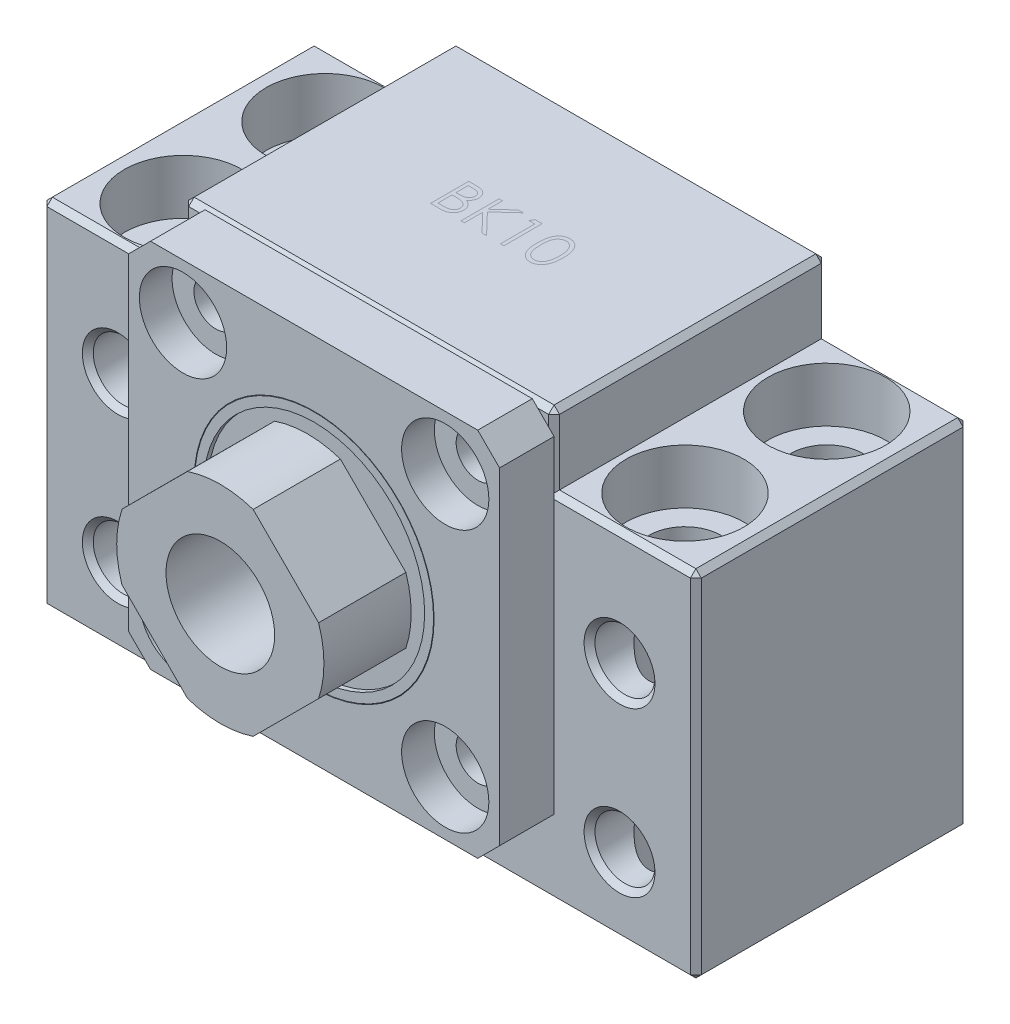
SolidWorks part; units mm, degrees
material "1060 Alloy"
ref_plane "Front Plane" through (0, 0, 0) normal (0, 0, 1) x (1, 0, 0)
ref_plane "Top Plane" through (0, 0, 0) normal (0, 1, 0) x (1, 0, 0)
ref_plane "Right Plane" through (0, 0, 0) normal (1, 0, 0) x (0, 0, -1)
ref_plane "Plane1" through (0, 0, -10) normal (0, 0, -1) x (-1, 0, 0)
sketch "Sketch1" plane through (0, 0, -10) normal (0, 0, -1) x (-1, 0, 0)
  line L0 (30, 0) -> (30, 39) construction
  line L1 (30, 39) -> (-30, 39) construction
  line L2 (-30, 39) -> (-30, 0) construction
  line L3 (-30, 0) -> (30, 0)
  line L4 (30, 32.5) -> (-30, 32.5) construction
  line L5 (0, 39) -> (0, 0) construction
  line L6 (-17, 39) -> (-17, 32.5)
  line L7 (17, 39) -> (17, 32.5)
  line L8 (30, 0) -> (30, 32.5)
  line L9 (-30, 32.5) -> (-30, 0)
  line L10 (-17, 39) -> (17, 39)
  line L11 (30, 32.5) -> (17, 32.5)
  line L12 (-30, 32.5) -> (-17, 32.5)
  line L13 (17, 39) -> (17, 0) construction
  line L14 (-17, 39) -> (-17, 0) construction
  line L16 (23, 7) -> (-23, 7) construction
  line L17 (23, 7) -> (23, 22) construction
  line L18 (23, 22) -> (-23, 22) construction
  line L19 (-23, 7) -> (-23, 22) construction
  line L20 (23, 7) -> (-23, 22) construction
  line L21 (23, 22) -> (-23, 7) construction
  circle A0 centre (-23, 22) radius 2.75
  circle A1 centre (23, 22) radius 2.75
  circle A2 centre (23, 7) radius 2.75
  circle A3 centre (-23, 7) radius 2.75
  point P4 (-30, 19.5)
  point P14 (0, 14.5)
  dimension "D9" = 5.5
  dimension "D10" = 5.5
  dimension "D11" = 5.5
  dimension "D12" = 5.5
  dimension "D1" = 60
  dimension "D2" = 39
  dimension "D3" = 32.5
  dimension "D6" = 15
  dimension "D7" = 22
  dimension "D8" = 46
  dimension "D4" = 17
  dimension "D5" = 17
extrude "Boss-Extrude1" add sketch "Sketch1" against normal blind 25
hole_wizard "Hole1" positions "Sketch5" profile "Sketch4" legacy
sketch "Sketch5" plane through (0, 0, 15) normal (0, 0, -1) x (-1, 0, 0)
  line L0 (30, 0) -> (30, 32.5) construction
  line L1 (-30, 0) -> (30, 0) construction
  point P0 (0, 22)
  dimension "D1" = 30
  dimension "D2" = 22
sketch "Sketch4" plane through (0, 22, 15) normal (1, 0, 0) x (0, -1, 0)
  line L0 (0, 0) -> (0, 25)
  line L1 (0, 25) -> (10.5, 25)
  line L2 (10.5, 25) -> (10.5, 20)
  line L3 (10.5, 20) -> (13, 20)
  line L4 (13, 20) -> (13, 0)
  line L5 (13, 0) -> (0, 0)
  line L6 (0, 110) -> (0, -10) construction
  dimension "Diameter" = 21
  dimension "C-Bore Diameter" = 26
  dimension "C-Bore Depth" = 20
sketch "Sketch10" plane through (0, 32.5, 0) normal (0, 1, 0) x (1, 0, 0)
  line L0 (-30, 4) -> (30, 4) construction
  line L3 (0, 10) -> (0, -15) construction
  line L4 (-17, 10) -> (17, 10) construction
  line L5 (-17, -15) -> (17, -15) construction
  line L7 (17, 10) -> (30, 10) construction
  line L8 (-30, -9) -> (30, -9) construction
  line L9 (-30, -15) -> (-30, 10) construction
  line L10 (30, -15) -> (30, 10) construction
  circle A0 centre (-23, 4) radius 3.3
  circle A1 centre (23, 4) radius 3.3
  circle A2 centre (-23, -9) radius 3.3
  circle A3 centre (23, -9) radius 3.3
  dimension "D1" = 6.6
  dimension "D2" = 6.6
  dimension "D3" = 46
  dimension "D4" = 23
  dimension "D7" = 6.6
  dimension "D8" = 6.6
  dimension "D5" = 6
  dimension "D6" = 13
extrude "Cut-Extrude3" cut sketch "Sketch10" against normal through all
sketch "Sketch11" plane through (0, 32.5, 0) normal (0, 1, 0) x (1, 0, 0)
  circle A0 centre (-23, 4) radius 5.4
  circle A1 centre (23, 4) radius 5.4
  circle A2 centre (-23, -9) radius 5.4
  circle A3 centre (23, -9) radius 5.4
  dimension "D1" = 10.8
  dimension "D2" = 10.8
  dimension "D3" = 10.8
  dimension "D4" = 10.8
extrude "Cut-Extrude4" cut sketch "Sketch11" against normal blind 5
chamfer "Chamfer3" distance 0.5 angle 45 32 edges at (0, 0, -10) (30, 16.25, -10) (23.5, 32.5, -10) (17, 35.75, -10) (0, 39, -10) (-17, 35.75, -10) (-23.5, 32.5, -10) (-30, 16.25, -10) (20.25, 22, -10) (-25.75, 22, -10) (-25.75, 7, -10) (20.25, 7, -10) (-23.5, 32.5, 15) (-17, 35.75, 15) (0, 39, 15) (17, 35.75, 15) (23.5, 32.5, 15) (30, 16.25, 15) (0, 0, 15) (-30, 16.25, 15) (20.25, 22, 15) (-25.75, 22, 15) (-25.75, 7, 15) (20.25, 7, 15) (-30, 32.5, 2.5) (-30, 0, 2.5) (30, 0, 2.5) (30, 32.5, 2.5) (17, 39, 2.5) (-17, 39, 2.5) (13, 22, 15) (10.5, 22, -10)
sketch "Sketch14" plane through (0, 0, 15) normal (0, 0, 1) x (1, 0, 0)
  line L0 (-15, 39) -> (-17, 37)
  line L1 (15, 5) -> (-15, 5)
  line L2 (17, 7) -> (17, 37)
  line L3 (15, 39) -> (-15, 39)
  line L4 (-17, 7) -> (-17, 37)
  line L5 (17, 5) -> (-17, 39) construction
  line L6 (17, 39) -> (-17, 5) construction
  line L7 (17, 37) -> (15, 39)
  line L8 (15, 5) -> (17, 7)
  line L9 (-15, 5) -> (-17, 7)
  circle A0 centre (0, 22) radius 17 construction
  circle A1 centre (-12.0208, 9.9792) radius 2
  circle A2 centre (12.0208, 9.9792) radius 2
  circle A3 centre (12.0208, 34.0208) radius 2
  circle A4 centre (-12.0208, 34.0208) radius 2
  circle A5 centre (0, 22) radius 11
  point P0 (0, 22)
  point P24 (12.0208, 9.9792)
  point P25 (12.0208, 9.9792)
  dimension "D3" = 4
  dimension "D4" = 4
  dimension "D5" = 4
  dimension "D6" = 4
  dimension "D11" = 22
  dimension "D1" = 34
  dimension "D2" = 34
  dimension "D12" = 17
extrude "Boss-Extrude2" add sketch "Sketch14" along normal blind 5 separate body
sketch "Sketch15" plane through (0, 0, 20) normal (0, 0, 1) x (1, 0, 0)
  circle A0 centre (-12.0208, 34.0208) radius 4
  circle A1 centre (12.0208, 34.0208) radius 4
  circle A2 centre (-12.0208, 9.9792) radius 4
  circle A3 centre (12.0208, 9.9792) radius 4
  dimension "D1" = 8
  dimension "D2" = 8
  dimension "D3" = 8
  dimension "D4" = 8
extrude "Cut-Extrude5" cut sketch "Sketch15" against normal blind 3
sketch "Sketch16" plane through (0, 0, 0) normal (1, 0, 0) x (0, 0, -1)
  line L0 (-15, 22) -> (9.0178, 22) construction
  line L1 (-19.5729, 15) -> (-20.6, 15)
  line L2 (-20.6, 15) -> (-20.6, 12.5)
  line L3 (5, 17) -> (10.4, 17)
  line L4 (5, 32.5) -> (5, 11.5) construction
  line L5 (10.4, 17) -> (10.4, 14.996)
  line L6 (10.4, 14.996) -> (8.3452, 14.996)
  line L7 (8.3452, 14.996) -> (8.3452, 13.0547)
  line L8 (8.3452, 13.0547) -> (9.5052, 13.0547)
  line L9 (9.5052, 13.0547) -> (9.5052, 11.4536)
  line L10 (9.5052, 11.4536) -> (5, 11.4536)
  line L11 (5, 11.4536) -> (5, 13.0747)
  line L12 (5, 13.0747) -> (6.0458, 13.0747)
  line L13 (6.0458, 13.0747) -> (6.0458, 15)
  line L14 (6.0458, 15) -> (5, 15)
  line L15 (5, 35) -> (5, 9) construction
  line L16 (5, 15) -> (5, 17)
  line L17 (10, 32) -> (10, 0.5) construction
  line L18 (5, 17) -> (5, 8.8785)
  line L19 (5, 8.8785) -> (-11, 8.8785)
  line L20 (-11, 8.8785) -> (-11, 17)
  line L21 (-11, 17) -> (5, 17)
  line L22 (-19.5729, 15) -> (-19.5729, 11.8671)
  line L23 (-19.5729, 11.8671) -> (-20, 11.8671)
  line L24 (-20, 37) -> (-20, 7) construction
  line L25 (-20.6, 17.02) -> (-20.6, 16.6237)
  line L26 (-16.6, 15.016) -> (-14.4452, 15.016)
  line L27 (-14.4452, 15.016) -> (-14.4452, 13.0747)
  line L28 (-14.4452, 13.0747) -> (-15.538, 13.0747)
  line L29 (-15.538, 13.0747) -> (-15.538, 10.9304)
  line L30 (-15.538, 10.9304) -> (-11.1266, 10.9304)
  line L31 (-11.1266, 10.9304) -> (-11.1266, 13.0746)
  line L32 (-11.1266, 13.0746) -> (-12.2547, 13.0746)
  line L33 (-12.2547, 13.0746) -> (-12.2547, 15.0199)
  line L34 (-12.2547, 15.0199) -> (-11.1373, 15.0199)
  line L35 (-11.1373, 15.0199) -> (-11.1373, 17.02)
  line L36 (-11.1373, 17.02) -> (-16.6, 17.02)
  line L37 (-16.6, 17.02) -> (-16.6, 15.016)
  line L38 (-20.6, 16.6237) -> (-16.7129, 16.6237)
  line L40 (-16.7129, 16.6237) -> (-16.7129, 15.02)
  line L41 (-20.6, 12.5) -> (-28.6, 12.5)
  line L42 (-28.6, 12.5) -> (-28.6, 17.02)
  line L43 (-28.6, 17.02) -> (-20.6, 17.02)
  line L44 (-20, 11.8671) -> (-20, 11.0464)
  line L45 (-20, 11.0464) -> (-19.7865, 10.9304)
  line L46 (-19.7865, 10.9304) -> (-16.7129, 10.9304)
  line L47 (-16.7129, 10.9304) -> (-16.7129, 15.02)
  point P7 (5.5229, 15)
  dimension "D1" = 22
  dimension "D2" = 5
  dimension "D3" = 2
  dimension "D4" = 0.4
  dimension "D5" = 10.5464
  dimension "D6" = 16
  dimension "D7" = 27
  dimension "D8" = 31
  dimension "D9" = 9.5
  dimension "D10" = 8
  dimension "D11" = 7
revolve "Revolve1" add sketch "Sketch16" angle 360 about L0 region at (0, 14.4747, 22.4984) region at (0, 14.405, -7.455) region at (0, 12.9393, 3) region at (0, 14.1373, 13.5738)
sketch "Sketch17" plane through (0, 0, 28.6) normal (0, 0, 1) x (1, 0, 0)
  line L0 (0, 31.5) -> (0, 12.5) construction
  line L1 (0, 12.5) -> (9.5, 22) construction
  line L2 (9.5, 22) -> (0, 31.5) construction
  line L3 (0, 31.5) -> (-9.5, 22.02) construction
  line L4 (-9.5, 22.02) -> (0, 12.5) construction
  line L5 (-1.9854, 32.037) -> (-10.0673, 23.972)
  line L6 (-10.1127, 20.1106) -> (-2.0038, 11.9846)
  line L7 (2.0054, 11.9846) -> (10.0581, 20.0373)
  line L8 (10.0581, 23.9627) -> (1.9838, 32.037)
  line L9 (0.0013, 34.0195) -> (-12.0208, 22.0227) construction
  line L10 (-12.0208, 22.0227) -> (-0.0013, 9.9779) construction
  line L11 (-0.0013, 9.9779) -> (12.0208, 22) construction
  line L12 (12.0208, 22) -> (0.0013, 34.0195) construction
  line L13 (-1.9854, 32.037) -> (1.9838, 32.037)
  line L14 (-10.0673, 23.972) -> (-10.1127, 20.1106)
  line L15 (-2.0038, 11.9846) -> (2.0054, 11.9846)
  line L16 (10.0581, 23.9627) -> (10.0581, 20.0373)
  circle A0 centre (0, 22) radius 9.5 construction
  circle A1 centre (0, 22) radius 11
  dimension "D3" = 22
  dimension "D1" = 13.435
  dimension "D2" = 1.7825
extrude "Cut-Extrude6" cut sketch "Sketch17" against normal blind 8
sketch "Sketch18" plane through (0, 39, 0) normal (0, 1, 0) x (1, 0, 0)
  text T0 "BK10"
wrap "Wrap1" sketch "Sketch18" wrap type scribe source sketch "Sketch18" face at (0, 39, 2.5)
